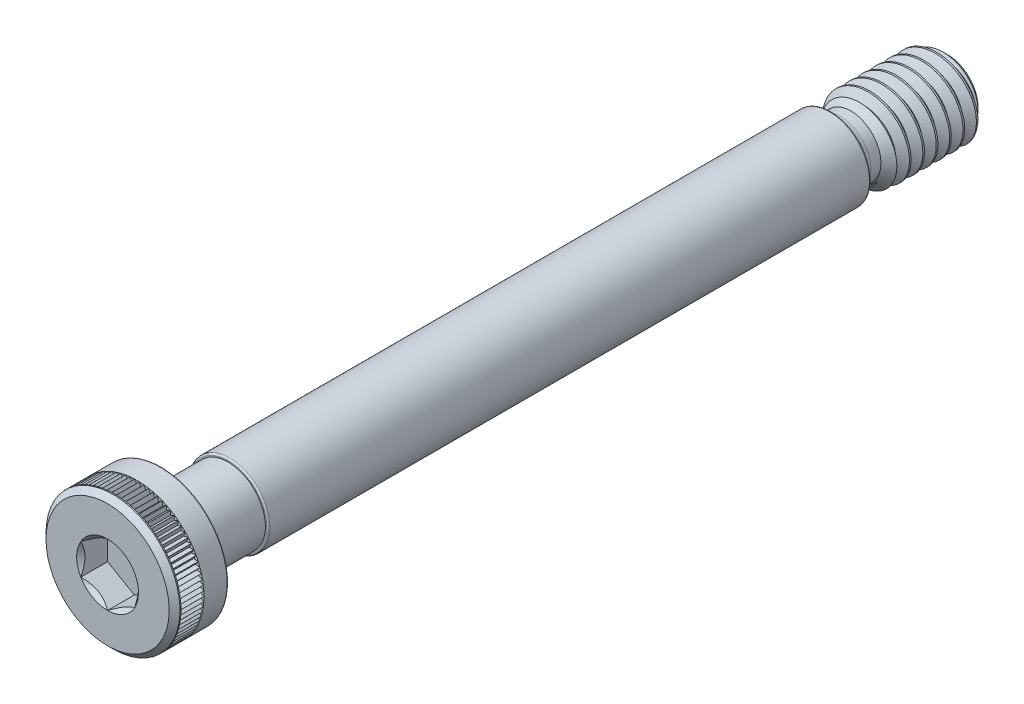
SolidWorks part; units mm, degrees
other "DetailItem1"
other "DetailItem2"
other "DetailItem5"
other "DetailItem6"
ref_plane "Front" through (0, 0, 0) normal (0, 0, 1) x (1, 0, 0)
ref_plane "Top" through (0, 0, 0) normal (0, 1, 0) x (1, 0, 0)
ref_plane "Right" through (0, 0, 0) normal (1, 0, 0) x (0, 0, -1)
sketch "Sketch1" plane through (0, 0, 0) normal (1, 0, 0) x (0, 0, -1)
  line L7 (-15.6875, 0) -> (15.6875, 0) construction
  line L8 (15.6875, 1.125) -> (15.3125, 1.5)
  line L9 (15.6563, 1.5541) -> (15.9063, 1.1211) construction
  line L16 (15.9063, 1.1211) -> (16.1563, 1.5541) construction
  line L22 (15.6875, 1.5) -> (15.6875, 0)
  line L23 (-13.6875, 2.5) -> (-13.6875, 1.395)
  line L24 (-13.6875, 1.395) -> (-11.1875, 1.395)
  line L25 (16.1563, 1.5541) -> (15.6563, 1.5541) construction
  line L26 (11.6875, 1.125) -> (12.0625, 1.125)
  line L27 (12.0625, 1.125) -> (12.4375, 1.5)
  line L29 (-15.6875, 2.5) -> (-15.6875, 0)
  line L30 (-15.6875, 2.5) -> (-13.6875, 2.5)
  line L33 (-11.1875, 1.5) -> (-11.1875, 1.395)
  line L34 (-11.1875, 1.5) -> (11.3125, 1.5)
  line L35 (15.6875, 1.5) -> (12.4375, 1.5)
  line L37 (15.6719, 1.5271) -> (16.1406, 1.5271)
  line L38 (16.1406, 1.5271) -> (15.9375, 1.1752)
  line L39 (15.9375, 1.1752) -> (15.875, 1.1752)
  line L40 (15.875, 1.1752) -> (15.6719, 1.5271)
  line L41 (15.9063, 1.1752) -> (15.9063, 1.1211) construction
  line L42 (15.6875, 1.5) -> (16.125, 1.5) construction
  line L47 (15.9063, 1.5541) -> (15.9063, 1.5) construction
  line L48 (11.3125, 1.5) -> (11.6875, 1.5) construction
  line L49 (-15.4875, 2.5) -> (-15.6875, 2.3)
  line L50 (15.6875, -1.5) -> (12.4375, -1.5)
  line L51 (-15.4475, 2.5) -> (-15.4475, 2.3) construction
  line L52 (-15.4475, 2.3) -> (-13.7275, 2.3) construction
  line L53 (-14.5875, 2.3) -> (-14.5875, 2.5) construction
  arc A0 (11.3125, 1.5) -> (11.6875, 1.125) centre (11.6875, 1.5) ccw
  arc A1 (11.2567, 1.5) -> (11.3161, 1.4483) centre (11.2567, 1.44) cw
  arc A2 (-11.1875, 1.44) -> (-11.1275, 1.5) centre (-11.1275, 1.44) cw
  arc A4 (-13.7275, 2.5) -> (-13.6875, 2.46) centre (-13.7275, 2.46) cw
  point P2 (0, 0)
  point P20 (15.9063, 1.5271)
  point P44 (-14.5875, 2.5)
  point P45 (15.6875, 1.5)
  point P46 (-15.4475, 2.5)
  point P47 (-13.6875, 1.9475)
  point P48 (12.0625, 1.9475)
  point P51 (-14.6875, 0)
  point P52 (14.6875, 1.5)
  point P54 (15.6875, 1.9475)
  point P57 (15.6875, -1.9475)
  point P58 (12.0625, -1.9475)
  dimension "D6" = 0.06
  dimension "D8" = 0.04
  dimension "D1" = 45
  dimension "Pitch" = 0.5
  dimension "D3" = 0.0625
  dimension "D2" = 0.375
  dimension "D4" = 2.79
  dimension "D5" = 2.5
  dimension "D9" = 0.2
  dimension "D12" = 0.04
  dimension "D10" = 1
  dimension "D11" = 1
  dimension "Shoulder Diameter" = 3
  dimension "Thread Length" = 4
sketch "Sketch2" plane through (0, 0, 0) normal (0, 0, 1) x (1, 0, 0)
  line L9 (0, 1.1547) -> (-1, 0.5774)
  line L11 (-0.0873, 2.5) -> (0.0873, 2.5)
  line L12 (0.0873, 2.5) -> (0, 2.3488)
  line L13 (0, 2.3488) -> (-0.0873, 2.5)
  line L14 (0, 0) -> (-0.0873, 2.5) construction
  line L15 (0, 0) -> (0.0873, 2.5) construction
  line L16 (-1, 0.5774) -> (-1, -0.5774)
  line L17 (-1, -0.5774) -> (0, -1.1547)
  line L18 (0, -1.1547) -> (1, -0.5774)
  line L19 (1, -0.5774) -> (1, 0.5774)
  line L20 (1, 0.5774) -> (0, 1.1547)
  circle A0 centre (0, 0) radius 1 construction
  circle A2 centre (0, 0) radius 2.5
sketch "Sketch12" plane through (0, 0, 0) normal (1, 0, 0) x (0, 0, -1)
  line L0 (-15.6875, 0) -> (-15.6875, 2.3)
  line L1 (-15.6875, 2.3) -> (-15.4875, 2.5)
  line L2 (-15.4875, 2.5) -> (-13.7275, 2.5)
  line L3 (15.6875, 1.125) -> (15.3125, 1.5) construction
  line L5 (12.0625, 1.125) -> (12.4375, 1.5) construction
  line L7 (11.6875, 1.125) -> (12.0625, 1.125) construction
  line L8 (15.6875, 1.125) -> (15.3125, 1.5)
  line L9 (12.0625, 1.125) -> (12.4375, 1.5)
  line L11 (11.6875, 1.125) -> (12.0625, 1.125)
  line L12 (-13.6875, 1.395) -> (-13.6875, 2.46)
  line L13 (-13.6875, 1.395) -> (-11.1875, 1.395)
  line L14 (-11.1875, 1.395) -> (-11.1875, 1.44)
  line L15 (-11.1275, 1.5) -> (11.2567, 1.5)
  line L16 (12.4375, 1.5) -> (15.3125, 1.5)
  line L17 (15.6875, 1.125) -> (15.6875, 0)
  line L18 (15.6875, 0) -> (-15.6875, 0)
  arc A0 (-13.6875, 2.46) -> (-13.7275, 2.5) centre (-13.7275, 2.46) ccw construction
  arc A1 (-13.6875, 2.46) -> (-13.7275, 2.5) centre (-13.7275, 2.46) ccw
  arc A5 (11.3125, 1.5) -> (11.6875, 1.125) centre (11.6875, 1.5) ccw construction
  arc A6 (11.3161, 1.4483) -> (11.2567, 1.5) centre (11.2567, 1.44) ccw construction
  arc A7 (-11.1275, 1.5) -> (-11.1875, 1.44) centre (-11.1275, 1.44) ccw construction
  arc A8 (11.3161, 1.4483) -> (11.6875, 1.125) centre (11.6875, 1.5) ccw
  arc A9 (11.3161, 1.4483) -> (11.2567, 1.5) centre (11.2567, 1.44) ccw
  arc A10 (-11.1275, 1.5) -> (-11.1875, 1.44) centre (-11.1275, 1.44) ccw
revolve "Revolve1" add sketch "Sketch12" angle 360 mid plane about L18
sketch "Sketch8" plane through (0, 0, 15.6875) normal (0, 0, 1) x (1, 0, 0)
  line L6 (0, -1.1547) -> (1, -0.5774) construction
  line L7 (-1, -0.5774) -> (0, -1.1547) construction
  line L8 (-1, 0.5774) -> (-1, -0.5774) construction
  line L9 (0, 1.1547) -> (-1, 0.5774) construction
  line L10 (1, 0.5774) -> (0, 1.1547) construction
  line L11 (1, -0.5774) -> (1, 0.5774) construction
  line L12 (0, -1.1547) -> (1, -0.5774)
  line L13 (-1, -0.5774) -> (0, -1.1547)
  line L14 (-1, 0.5774) -> (-1, -0.5774)
  line L15 (0, 1.1547) -> (-1, 0.5774)
  line L16 (1, 0.5774) -> (0, 1.1547)
  line L17 (1, -0.5774) -> (1, 0.5774)
extrude "Cut-Extrude2" cut sketch "Sketch8" against normal up to vertex (1 mm away) up to point (0, 0, 14.6875)
sketch "Sketch9" plane through (0, 0, 15.6875) normal (0, 0, 1) x (1, 0, 0)
  circle A1 centre (0, 0) radius 1.1547
extrude "Cut-Extrude4" cut sketch "Sketch9" against normal up to vertex (1 mm away) draft 45 up to point (0, 0, 14.6875)
ref_axis "Center Axis1" through (0, 0, -15.224) along (0, 0, 1)
ref_plane "Contact Plane1" through (0, 0, -15.6875) normal (0, 0, 1) x (1, 0, 0)
ref_plane "Contact Plane2" through (0, 0, 13.6875) normal (0, 0, 1) x (1, 0, 0)
ref_plane "Plane2" through (0, 0, -12.0625) normal (0, 0, -1) x (-1, 0, 0)
split "Split1" trim tools "Plane2" bodies to split 118 resulting bodies 122 123
sketch "Sketch3" plane through (0, 0, -15.6875) normal (0, 0, 1) x (1, 0, 0)
  circle A0 centre (0, 0) radius 1.5 construction
  circle A2 centre (0, 0) radius 1.5
curve "Helix/Spiral1" pitch 0.5 height 4 radius 1.5 centre (0, 0, -15.6875) axis (0, 0, 1) start towards (0, 1, 0)
sketch "Sketch13" plane through (0, 0, 0) normal (1, 0, 0) x (0, 0, -1)
  line L0 (15.6719, 1.5271) -> (16.1406, 1.5271) construction
  line L1 (15.875, 1.1752) -> (15.6719, 1.5271) construction
  line L2 (15.9375, 1.1752) -> (15.875, 1.1752) construction
  line L3 (16.1406, 1.5271) -> (15.9375, 1.1752) construction
  line L16 (15.6719, 1.5271) -> (16.1406, 1.5271)
  line L17 (15.875, 1.1752) -> (15.6719, 1.5271)
  line L18 (15.9375, 1.1752) -> (15.875, 1.1752)
  line L19 (16.1406, 1.5271) -> (15.9375, 1.1752)
sweep "Cut-Sweep1" cut profiles "Sketch13" path "Helix/Spiral1" align with end faces yes
combine bodies "Combine1" operation type add bodies to combine 123 126
ref_plane "Plane1" through (0, 0, 15.4475) normal (0, 0, 1) x (1, 0, 0)
sketch "Sketch11" plane through (0, 0, 15.4475) normal (0, 0, 1) x (1, 0, 0)
  line L0 (0.0873, 2.5) -> (0, 2.3488) construction
  line L1 (0, 2.3488) -> (-0.0873, 2.5) construction
  line L2 (-0.0873, 2.5) -> (0.0873, 2.5) construction
  line L3 (0.0873, 2.5) -> (0, 2.3488)
  line L4 (0, 2.3488) -> (-0.0873, 2.5)
  line L5 (-0.0873, 2.5) -> (0.0873, 2.5)
  point P3 (0, 0.0018)
  point P8 (2.3908, 0.7309)
extrude "Cut-Extrude5" cut sketch "Sketch11" against normal up to vertex (0.86 mm away) up to point (0, 2.5, 14.5875)
pattern_circular "CirPattern1" count 90 over 360 about axis through (0, 0, 15.4875) along (0, 0, -1) of "Cut-Extrude5"
equation "\"D3@Sketch1\"=\"Pitch@Sketch1\"/8"
equation "\"D2@Sketch1\"=\"Pitch@Sketch1\"*.75"
equation "\"D4@Sketch1\"=\"Shoulder Diameter@Sketch1\"*.93"
equation "\"D5@Sketch1\"=\"Shoulder Length@Sketch1\"*.1"
equation "\"D6@Sketch1\"=\"Shoulder Diameter@Sketch1\"*.04*0.5"
equation "\"D8@Sketch1\"=\"Head Height@Sketch1\"*.02"
equation "\"D9@Sketch1\"=\"Head Height@Sketch1\"*.1"
equation "\"D4@Helix/Spiral1\"=\"Pitch@Sketch1\""
equation "\"D3@Helix/Spiral1\"=\"Thread Length@Sketch1\""
equation "\"D1@CirPattern1\" = 360 / \"Knurl Angle@Sketch2\""
equation "\"D12@Sketch1\"=\"Head Height@Sketch1\"*.02"
equation "\"D10@Sketch1\"=\"Pitch@Sketch1\"*2"
equation "\"D11@Sketch1\"=\"Head Height@Sketch1\"*0.5"
